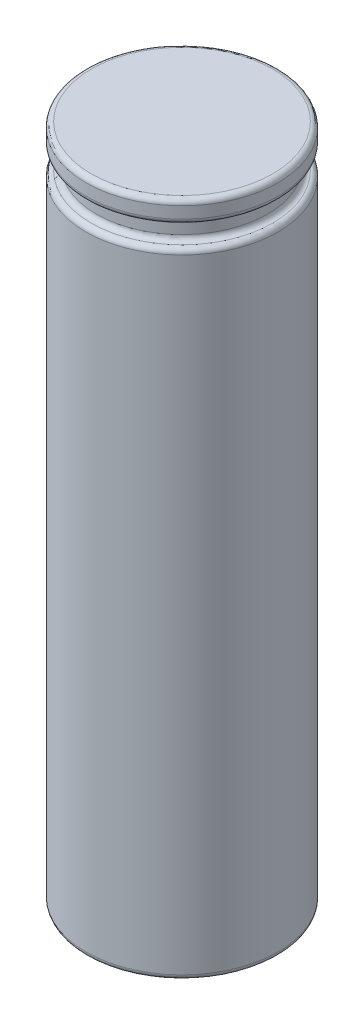
SolidWorks part; units mm, degrees
ref_plane "Front Plane" through (0, 0, 0) normal (0, 0, 1) x (1, 0, 0)
ref_plane "Top Plane" through (0, 0, 0) normal (0, 1, 0) x (1, 0, 0)
ref_plane "Right Plane" through (0, 0, 0) normal (1, 0, 0) x (0, 0, -1)
sketch "Sketch1" plane through (0, 0, 0) normal (0, 1, 0) x (1, 0, 0)
  circle A0 centre (0, 0) radius 9.25
  dimension "D1" = 18.5
extrude "Boss-Extrude1" add sketch "Sketch1" along normal blind 65.2
sketch "Sketch2" plane through (0, 0, 0) normal (1, 0, 0) x (0, 0, -1)
  line L0 (9.25, 0) -> (9.25, 65.2) construction
  line L1 (9.25, 63.0869) -> (8.25, 63.0869)
  line L2 (9.25, 63.0869) -> (9.25, 61.0869)
  line L3 (9.25, 61.0869) -> (8.25, 61.0869)
  line L4 (8.25, 63.0869) -> (8.25, 61.0869)
  line L5 (9.25, 0) -> (9.25, 65.2) construction
  line L6 (9.25, 0) -> (9.25, 65.2) construction
  dimension "D1" = 2
  dimension "D2" = 1
ref_axis "Axis1" through (0, 65.2, 0) along (0, -1, 0)
revolve "Cut-Revolve1" cut sketch "Sketch2" angle 360 about axis through (0, 65.2, 0) along (0, -1, 0)
fillet "Fillet1" radius 0.5 6 edges at (0, 0, 9.25) (0, 65.2, 9.25) (0, 63.0869, 9.25) (0, 63.0869, 8.25) (0, 61.0869, 8.25) (0, 61.0869, 9.25)
